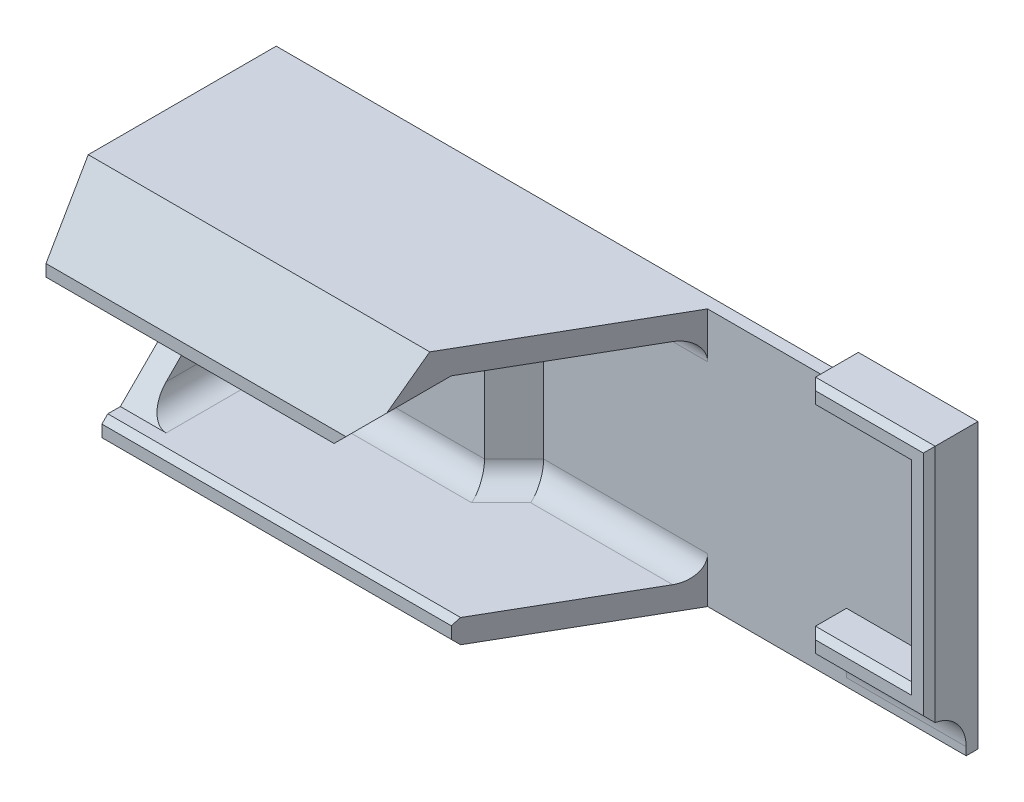
SolidWorks part; units mm, degrees
ref_plane "Front Plane" through (0, 0, 0) normal (0, 0, 1) x (1, 0, 0)
ref_plane "Top Plane" through (0, 0, 0) normal (0, 1, 0) x (1, 0, 0)
ref_plane "Right Plane" through (0, 0, 0) normal (1, 0, 0) x (0, 0, -1)
sketch "Sketch1" plane through (0, 0, 0) normal (1, 0, 0) x (0, 0, -1)
  line L0 (-9, 9.5) -> (13, 9.5)
  line L1 (-9, -9.5) -> (9, -9.5) construction
  line L2 (-9, -9.5) -> (-9, 9.5) construction
  line L3 (-9, 9.5) -> (9, 9.5) construction
  line L4 (9, -9.5) -> (9, 9.5) construction
  line L5 (0, 9.5) -> (0, -9.5) construction
  line L6 (-9, 0) -> (9, 0) construction
  line L7 (13, 9.5) -> (13, -19)
  line L8 (13, -19) -> (-9, -19)
  line L9 (-9, -19) -> (-9, -22.2)
  line L10 (-9, -22.2) -> (13, -22.2)
  line L11 (13, -22.2) -> (13, -37.2)
  line L12 (13, -37.2) -> (-3.0777, -53.2777)
  line L13 (-3.0777, -53.2777) -> (-1.4777, -54.8777)
  line L14 (-1.4777, -54.8777) -> (16.2, -37.2)
  line L15 (16.2, -37.2) -> (16.2, 12.7)
  line L16 (16.2, 12.7) -> (-10.8475, 12.7)
  line L17 (-10.8475, 12.7) -> (-17.2561, 1.6)
  line L18 (-17.2561, 1.6) -> (-14.4848, 0)
  line L19 (-14.4848, 0) -> (-9, 9.5)
  line L20 (13, 9.5) -> (16.2, 9.5) construction
  line L21 (13, 9.5) -> (13, 12.7) construction
  line L22 (-1.4777, -54.8777) -> (-1.4777, -51.6777) construction
  line L23 (-9, 9.5) -> (-11.7713, 11.1) construction
  line L24 (-14.4848, 0) -> (-14.4848, -19) construction
  point P0 (0, 0)
  point P4 (0, 0)
  point P24 (0, 0)
  point P25 (-15.6724, -2.057)
  point P26 (0, 0)
  point P27 (0, 0)
  point P28 (0, 0)
  point P29 (0, 0)
  point P30 (0, 0)
  point P31 (0, 0)
  point P32 (0, 0)
  dimension "D1" = 18
  dimension "D2" = 19
  dimension "D3" = 4
  dimension "D4" = 45
  dimension "D5" = 25
  dimension "D6" = 15
  dimension "D7" = 30
  dimension "D8" = 3.2
extrude "Boss-Extrude1" add sketch "Sketch1" along normal blind 60
sketch "Sketch2" plane through (60, 0, 0) normal (1, 0, 0) x (0, 0, -1)
  line L0 (-3.0777, -53.2777) -> (-1.4777, -54.8777)
  line L1 (-1.4777, -54.8777) -> (16.2, -37.2)
  line L2 (16.2, -37.2) -> (16.2, 12.7)
  line L3 (16.2, 12.7) -> (13, 12.7)
  line L4 (13, 12.7) -> (13, -37.2)
  line L5 (13, -37.2) -> (-3.0777, -53.2777)
extrude "Boss-Extrude2" add sketch "Sketch2" along normal blind 35
sketch "Sketch3" plane through (0, -22.2, 0) normal (0, -1, 0) x (1, 0, 0)
  line L0 (60, -13) -> (42.5316, 17.2561)
  line L1 (42.5316, 17.2561) -> (60, 17.2561)
  line L2 (60, 17.2561) -> (60, -13)
  dimension "D1" = 30
extrude "Cut-Extrude1" cut sketch "Sketch3" against normal through all
sketch "Sketch4" plane through (0, 0, 9) normal (0, 0, 1) x (1, 0, 0)
  line L0 (47.2983, 9.5) -> (37.7983, 0)
  line L1 (44.1316, 0) -> (0, 0) construction
  line L2 (37.7983, 0) -> (47.2983, 0)
  line L3 (47.2983, 0) -> (47.2983, 9.5)
extrude "Cut-Extrude2" cut sketch "Sketch4" along normal through all
sketch "Sketch5" plane through (0, 0, 0) normal (-1, 0, 0) x (0, 0, 1)
  line L0 (16.5633, 2.8) -> (16.5633, 1.2)
  line L1 (10.8475, 12.7) -> (17.2561, 1.6) construction
  line L2 (17.2561, 1.6) -> (14.4848, 0) construction
  line L3 (16.5633, 1.2) -> (17.2561, 1.6)
  line L4 (17.2561, 1.6) -> (16.5633, 2.8)
  line L5 (2.2777, -52.4777) -> (2.2777, -54.0777)
  line L6 (-13, -37.2) -> (3.0777, -53.2777) construction
  line L7 (3.0777, -53.2777) -> (1.4777, -54.8777) construction
  line L8 (2.2777, -54.0777) -> (3.0777, -53.2777)
  line L9 (3.0777, -53.2777) -> (2.2777, -52.4777)
  dimension "D1" = 1.6
extrude "Cut-Extrude3" cut sketch "Sketch5" against normal through all
sketch "Sketch6" plane through (0, 0, -13) normal (0, 0, 1) x (1, 0, 0)
  line L0 (78.8, 13) -> (91.8, 13)
  line L1 (91.8, 13) -> (91.8, -13)
  line L2 (91.8, -13) -> (78.8, -13)
  line L3 (78.8, -13) -> (78.8, -16.2)
  line L4 (78.8, -16.2) -> (95, -16.2)
  line L5 (95, -16.2) -> (95, 16.2)
  line L6 (95, 16.2) -> (78.8, 16.2)
  line L7 (78.8, 16.2) -> (78.8, 13)
  line L8 (91.8, 0) -> (95, 0) construction
  line L9 (0, -19) -> (0, -22.2) construction
  dimension "D1" = 26
  dimension "D2" = 13
extrude "Boss-Extrude3" add sketch "Sketch6" along normal blind 5 and the other way up to surface (3.2 mm away) other way up to face at (47.5, -12.25, -16.2)
sketch "Sketch7" plane through (0, 0, -16.2) normal (0, 0, -1) x (-1, 0, 0)
  line L0 (-95, 16.2) -> (-78.8, 16.2)
  line L1 (-78.8, 16.2) -> (-75.3, 12.7)
  line L2 (-91.8, 12.7) -> (0, 12.7) construction
  line L3 (-75.3, 12.7) -> (-95, 12.7)
  line L4 (-95, -37.2) -> (-95, 16.2) construction
  line L5 (-95, 12.7) -> (-95, 16.2)
  dimension "D1" = 45
extrude "Boss-Extrude4" add sketch "Sketch7" against normal up to surface (3.2 mm away) up to face at (55.0857, -12.2, -13)
sketch "Sketch9" plane through (0, -19, 0) normal (0, 1, 0) x (1, 0, 0)
  line L0 (33.7983, 9) -> (37.7983, 13)
  line L1 (37.7983, 13) -> (0, 13)
  line L2 (0, 13) -> (0, 9)
  line L3 (0, 9) -> (33.7983, 9)
  point P2 (0, 0)
  point P5 (0, 0)
  dimension "D1" = 45
extrude "Boss-Extrude5" add sketch "Sketch9" along normal up to surface (28.5 mm away) up to face at (26.8246, 9.5, -2)
sketch "Sketch10" plane through (0, 0, 0) normal (-1, 0, 0) x (0, 0, 1)
  line L0 (6.5, -19) -> (-3, -9.5)
  line L1 (-13, -19) -> (9, -19) construction
  line L2 (-3, -9.5) -> (-9, -9.5)
  line L3 (-9, -9.5) -> (-9, -19)
  line L4 (-9, -19) -> (6.5, -19)
  line L5 (9, -9.5) -> (-9, -9.5) construction
  point P4 (0, 0)
  point P10 (-4.9736, -9.5)
  dimension "D1" = 45
  dimension "D2" = 6
extrude "Boss-Extrude6" add sketch "Sketch10" against normal blind 3.2
sketch "Sketch8" plane through (0, 0, 0) normal (-1, 0, 0) x (0, 0, 1)
  line L0 (-16.2, -37.2) -> (-16.2, 12.7) construction
  line L1 (-16.2, -22.2) -> (9, -22.2)
  line L2 (-16.2, -22.2) -> (-16.2, -54.8777)
  line L3 (-16.2, -54.8777) -> (9, -54.8777)
  line L4 (9, -22.2) -> (9, -54.8777)
  line L5 (-3.6, -54.8777) -> (-3.6, -22.2) construction
  line L6 (-16.2, -38.5388) -> (9, -38.5388) construction
  point P148 (-3.6, -38.5388)
extrude "Cut-Extrude4" cut sketch "Sketch8" against normal through all
chamfer "Chamfer1" distance 0.8 angle 45 8 edges at (86.9, 16.2, -8) (95, 0, -8) (86.9, -16.2, -8) (78.8, -14.6, -8) (85.3, -13, -8) (91.8, 0, -8) (85.3, 13, -8) (78.8, 14.6, -8)
fillet "Fillet1" radius 5 1 edges at (86.9, -16.2, -13)
fillet "Fillet2" radius 3 7 edges at (35.7983, 9.5, -11) (35.7983, -19, -11) (18.4991, -19, -9) (48.8991, -19, -13) (48.8991, 9.5, -13) (16.8991, 9.5, -9) (1.6, -9.5, -9)
fillet "Fillet3" radius 3 3 edges at (3.2, -11.25, -9) (3.2, -18.1213, -8.1213) (3.2, -19, 0.25)
chamfer "Chamfer2" distance 1.6 angle 45 6 edges at (86.9, 16.2, -16.2) (77.05, 14.45, -16.2) (37.65, 12.7, -16.2) (0, -4.75, -16.2) (47.5, -22.2, -16.2) (95, -3, -16.2)
chamfer "Chamfer3" distance 0.8 angle 45 2 edges at (23.6491, -19, 9) (23.6491, -22.2, 9)
